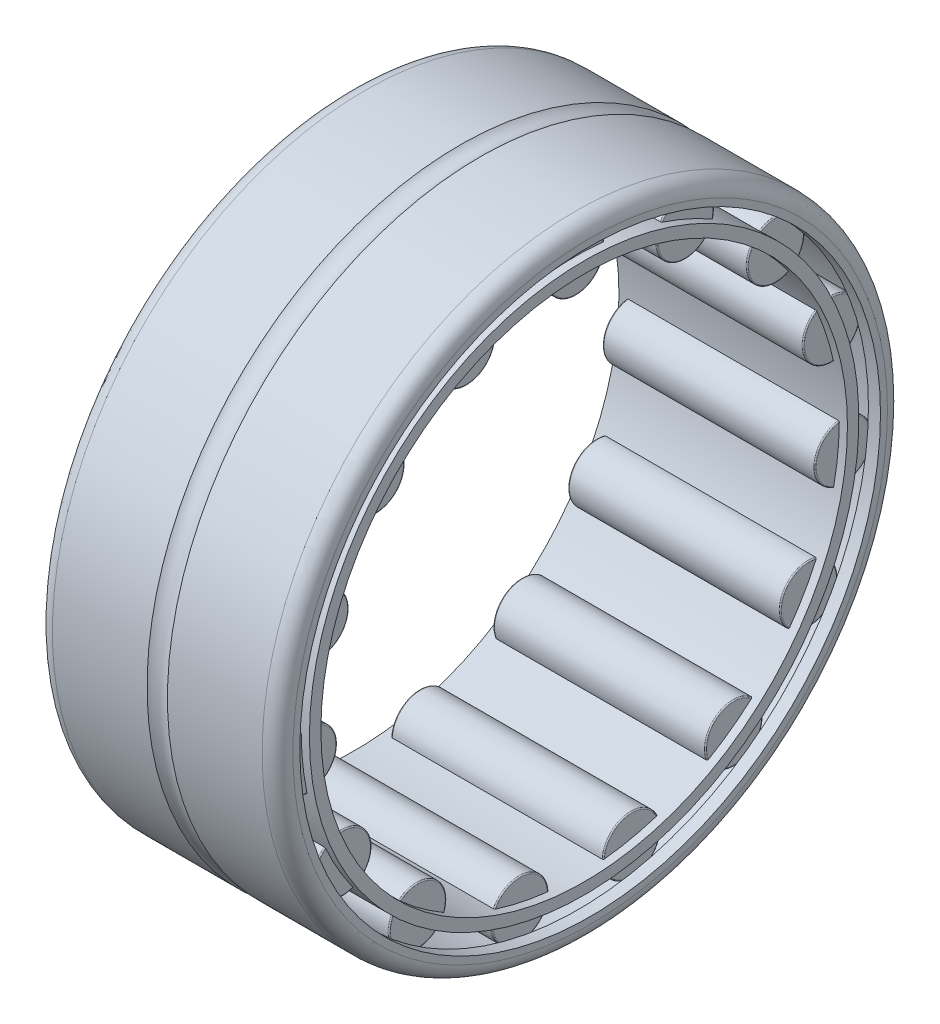
SolidWorks part; units mm, degrees
ref_plane "Plane1" through (0, 0, 0) normal (0, 0, 1) x (1, 0, 0)
ref_plane "Plane2" through (0, 0, 0) normal (0, 1, 0) x (1, 0, 0)
ref_plane "Plane3" through (0, 0, 0) normal (1, 0, 0) x (0, 0, -1)
sketch "Clipboard" plane through (0, 0, 0) normal (0, 0, 1) x (1, 0, 0)
  line L0 (-10, 0) -> (10, 0) construction
  line L1 (41.1529, 1.4371) -> (62.7517, -4.3503)
  line L2 (41.1529, 1.4371) -> (75.4583, 10.6292)
  line L3 (41.1529, 1.4371) -> (62.7517, -4.3503)
  line L4 (41.1529, 1.4371) -> (-22.3471, -0.7804)
  dimension "BallCLRad" = 35.5155
  dimension "Bore" = 63.5
sketch "InnRacSke" plane through (0, 0, 0) normal (0, 0, 1) x (1, 0, 0)
  line L0 (-14.2875, 38.3286) -> (-15.875, 38.3286)
  line L1 (-15.875, 38.3286) -> (-15.875, 39.243)
  line L2 (-13.843, 41.275) -> (-1.344, 41.275)
  line L3 (1.344, 41.275) -> (13.843, 41.275)
  line L4 (15.875, 39.243) -> (15.875, 38.3286)
  line L5 (15.875, 38.3286) -> (14.2875, 38.3286)
  line L6 (14.2875, 38.3286) -> (14.2875, 39.2811)
  line L7 (14.2875, 39.2811) -> (-14.2875, 39.2811)
  line L8 (-14.2875, 39.2811) -> (-14.2875, 38.3286)
  line L9 (-31.75, 0) -> (31.75, 0) construction
  arc A0 (-15.875, 39.243) -> (-13.843, 41.275) centre (-13.843, 39.243) cw
  arc A1 (-1.344, 41.275) -> (1.344, 41.275) centre (0, 42.799) ccw
  arc A2 (13.843, 41.275) -> (15.875, 39.243) centre (13.843, 39.243) cw
  dimension "D1" = 78.5622
revolve "Race" add sketch "InnRacSke" angle 360 about L9 reverse direction yes
sketch "RolDetSke" plane through (0, 0, 0) normal (0, 0, 1) x (1, 0, 0)
  line L0 (-14.0018, 39.1427) -> (-14.0017, 35.5155)
  line L1 (-14.0017, 35.5155) -> (14.0017, 35.5155)
  line L2 (14.0017, 35.5155) -> (14.0018, 39.1427)
  line L3 (13.8506, 39.2938) -> (-13.8506, 39.2938)
  line L4 (-28.575, 35.5155) -> (28.575, 35.5155) construction
  arc A0 (14.0018, 39.1427) -> (13.8506, 39.2938) centre (13.8506, 39.1427) ccw
  arc A1 (-13.8506, 39.2938) -> (-14.0018, 39.1427) centre (-13.8506, 39.1427) ccw
  dimension "Roller_length" = 28.0035
  dimension "Roller_diameter" = 7.5565
revolve "RollerDetailed" add sketch "RolDetSke" angle 360 about L4 reverse direction yes
ref_axis "Axis1" through (-50, 0, 0) along (1, 0, 0)
sketch "CagSpiSke" plane through (0, 0, 0) normal (0, 0, 1) x (1, 0, 0)
  line L0 (15.0812, 34.7599) -> (15.0812, 36.2712)
  line L1 (15.0812, 36.2712) -> (-15.0813, 36.2712)
  line L2 (-15.0813, 36.2712) -> (-15.0813, 34.7599)
  line L3 (-15.0813, 34.7599) -> (15.0812, 34.7599)
  line L4 (-31.75, 0) -> (31.75, 0) construction
  dimension "D2" = 69.5198
  dimension "halfWidth" = 15.0812
revolve "CageSpine" add sketch "CagSpiSke" angle 360 about L4
pattern_circular "RollersDetailed" count 15 every 24 about axis through (-50, 0, 0) along (1, 0, 0) of "RollerDetailed"
sketch "RolSimSke" plane through (0, 0, 0) normal (0, 0, 1) x (1, 0, 0)
  line L0 (-25.4, 0) -> (25.4, 0) construction
  line L2 (-13.8506, 39.3065) -> (13.8506, 39.3065)
  line L3 (-14.0018, 39.1554) -> (-14.0018, 31.9011)
  line L4 (-13.8506, 31.75) -> (13.8506, 31.75)
  line L5 (14.0017, 39.1554) -> (14.0017, 31.9011)
  arc A0 (-14.0018, 31.9011) -> (-13.8506, 31.75) centre (-13.8506, 31.9011) ccw
  arc A1 (-13.8506, 39.3065) -> (-14.0018, 39.1554) centre (-13.8506, 39.1554) ccw
  arc A2 (14.0017, 39.1554) -> (13.8506, 39.3065) centre (13.8506, 39.1554) ccw
  arc A3 (13.8506, 31.75) -> (14.0017, 31.9011) centre (13.8506, 31.9011) ccw
  point P10 (-14.0018, 31.75)
  point P15 (14.0017, 39.3065)
  point P18 (14.0017, 31.75)
  dimension "Bore" = 63.5
  dimension "D1" = 0.1511
  dimension "Roller_length" = 28.0035
  dimension "Roller_diameter" = 7.5565
  dimension "halfWidth" = 14.0017
revolve "RollersSimplified" [suppressed] add sketch "RolSimSke" angle 360 about L0
equation "\"BallCLRad@Clipboard\" =  ( \"D1@InnRacSke\" + \"Bore@Clipboard\" )  / 4"
equation "\"RollerCLRad@RolDetSke\" = \"BallCLRad@Clipboard\""
equation "\"offset@InnRacSke\" = \"radius@InnRacSke\" * .75"
equation "\"halfCyl@InnRacSke\" = \"Cyl_Len@InnRacSke\" / 2"
equation "\"Roller_diameter@RolDetSke\" =  ( \"D1@InnRacSke\" - \"Bore@Clipboard\" )  / 2 + .001"
equation "\"Roller_radius@RolDetSke\" = \"Roller_diameter@RolDetSke\" / 50"
equation "\"Roller_length@RolDetSke\" = \"Cyl_Len@InnRacSke\" * .98"
equation "\"halfLength@RolDetSke\" = \"Roller_length@RolDetSke\" / 2"
equation "\"Cage_width@CagSpiSke\" =  ( \"Cyl_Len@InnRacSke\" + \"Width@InnRacSke\" )  / 2"
equation "\"halfWidth@CagSpiSke\" = \"Cage_width@CagSpiSke\" / 2"
equation "\"Cage_thickness@CagSpiSke\"  = \"Roller_diameter@RolDetSke\" / 5"
equation "\"D2@CagSpiSke\" =  \"RollerCLRad@RolDetSke\" * 2 - \"Cage_thickness@CagSpiSke\""
equation "\"Roller_length@RolSimSke\" = \"Cyl_Len@InnRacSke\" * .98"
equation "\"halfWidth@RolSimSke\" = \"Roller_length@RolSimSke\" / 2"
equation "\"D1@RolSimSke\" = \"Roller_radius@RolDetSke\""
equation "\"Roller_diameter@RolSimSke\" =  ( \"D1@InnRacSke\" - \"Bore@Clipboard\" )  / 2 + .001"
equation "\"Max_count@Clipboard\" = int( 3.14159265 / atn(( \"Roller_diameter@RolDetSke\" / 2) / sqr( \"RollerCLRad@RolDetSke\"  *  \"RollerCLRad@RolDetSke\" - ( \"Roller_diameter@RolDetSke\" / 2) *  ( \"Roller_diameter@RolDetSke\" / 2))))"
equation "\"Max_count@Clipboard\" = ((sgn( \"Max_count@Clipboard\" - \"Count@Clipboard\" )-1)*( \"Max_count@Clipboard\" - \"Count@Clipboard\" ))/-2+ \"Count@Clipboard\""
equation "\"Count@RollersDetailed\" = int( \"Show_count@Clipboard\" ) "
equation "\"Count@RollersDetailed\" = ((sgn( \"Count@RollersDetailed\" - \"Max_count@Clipboard\" )-1)*( \"Count@RollersDetailed\" - \"Max_count@Clipboard\" ))/-2+ \"Max_count@Clipboard\""
equation "\"Count@RollersDetailed\" = ((sgn( \"Count@RollersDetailed\" - \"Min_count@Clipboard\" )+1)*( \"Count@RollersDetailed\" - \"Min_count@Clipboard\"))/2 +\"Min_count@Clipboard\""
equation "\"Angle@RollersDetailed\" = 360.0 / \"Max_count@Clipboard\""
equation "\"Angle@CageSpine\" =  \"Angle@RollersDetailed\" * ( \"Count@RollersDetailed\" -1 + int( \"Count@RollersDetailed\" / \"Max_count@Clipboard\" ) )  + 0.001 -  int( \"Count@RollersDetailed\" / \"Max_count@Clipboard\" ) * 0.001"
equation "\"Angle@CageSpine\" =  \"Angle@CageSpine\" * int( \"Min_count@Clipboard\" / 2) + int(1 / \"Min_count@Clipboard\")  * 0.001"
equation "\"Bore@RolSimSke\" = \"Bore@Clipboard\""
